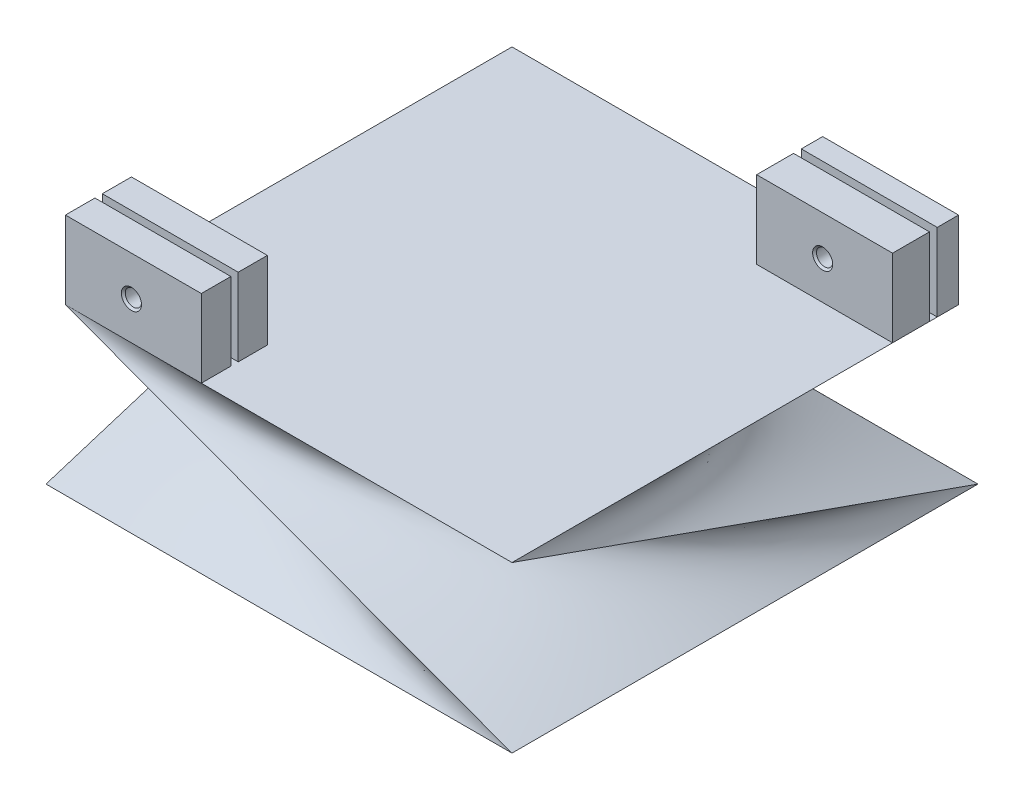
SolidWorks part; units mm, degrees
ref_plane "Front Plane" through (0, 0, 0) normal (0, 0, 1) x (1, 0, 0)
ref_plane "Top Plane" through (0, 0, 0) normal (0, 1, 0) x (1, 0, 0)
ref_plane "Right Plane" through (0, 0, 0) normal (1, 0, 0) x (0, 0, -1)
sketch "Sketch1" plane through (0, 0, 0) normal (0, 1, 0) x (1, 0, 0)
  line L1 (-76.2, -76.2) -> (76.2, -76.2)
  line L2 (-76.2, -76.2) -> (-76.2, 76.2)
  line L3 (-76.2, 76.2) -> (76.2, 76.2)
  line L4 (76.2, -76.2) -> (76.2, 76.2)
  line L5 (-76.2, -76.2) -> (76.2, 76.2) construction
  line L6 (-76.2, 76.2) -> (76.2, -76.2) construction
  point P0 (0, 0)
  dimension "D1" = 152.4
  dimension "D2" = 152.4
ref_plane "Plane1" through (0, 50.8, 0) normal (0, 1, 0) x (1, 0, 0)
sketch "Sketch2" plane through (0, 50.8, 0) normal (0, 1, 0) x (1, 0, 0)
  line L0 (-76.2, -76.2) -> (76.2, 76.2) construction
  line L1 (-73.025, -73.025) -> (73.025, -73.025)
  line L2 (-73.025, -73.025) -> (-73.025, 73.025)
  line L3 (-73.025, 73.025) -> (73.025, 73.025)
  line L4 (73.025, -73.025) -> (73.025, 73.025)
  line L5 (-73.025, -73.025) -> (73.025, 73.025) construction
  line L6 (-73.025, 73.025) -> (73.025, -73.025) construction
  point P0 (0, 0)
  dimension "D1" = 146.05
loft "Loft1" add profiles "Sketch2", "Sketch1" connector at (-73.025, 50.8, -73.025) connector at (-76.2, 0, 76.2)
sketch "Sketch20" plane through (0, 50.8, 0) normal (0, 1, 0) x (1, 0, 0)
  line L1 (-73.025, -73.025) -> (-28.575, -73.025)
  line L2 (-73.025, -73.025) -> (-73.025, -51.435)
  line L3 (-73.025, -51.435) -> (-28.575, -51.435)
  line L4 (-28.575, -73.025) -> (-28.575, -51.435)
  line L5 (73.025, 73.025) -> (28.575, 73.025)
  line L6 (73.025, 73.025) -> (73.025, 51.435)
  line L7 (73.025, 51.435) -> (28.575, 51.435)
  line L8 (28.575, 73.025) -> (28.575, 51.435)
  dimension "D1" = 44.45
  dimension "D2" = 21.59
  dimension "D3" = 44.45
  dimension "D4" = 21.59
extrude "Boss-Extrude3" add sketch "Sketch20" along normal blind 25.4
sketch "Sketch22" plane through (0, 76.2, 0) normal (0, 1, 0) x (1, 0, 0)
  line L0 (-28.575, -60.96) -> (-73.025, -60.96)
  line L1 (-28.575, -73.025) -> (-28.575, -51.435) construction
  line L2 (-73.025, -51.435) -> (-73.025, -73.025) construction
  line L3 (-73.025, -63.373) -> (-28.575, -63.373)
  line L4 (-73.025, -51.435) -> (-73.025, -73.025) construction
  line L5 (-28.575, -73.025) -> (-28.575, -51.435) construction
  line L6 (-28.575, -51.435) -> (-73.025, -51.435) construction
  line L7 (-73.025, -73.025) -> (-28.575, -73.025) construction
  line L8 (-28.575, -60.96) -> (-28.575, -63.373)
  line L9 (-73.025, -60.96) -> (-73.025, -63.373)
  dimension "D1" = 9.525
  dimension "D2" = 9.652
extrude "Cut-Extrude2" cut sketch "Sketch22" against normal blind 25.4
sketch "Sketch23" plane through (0, 76.2, 0) normal (0, 1, 0) x (1, 0, 0)
  line L0 (28.575, 66.04) -> (73.025, 66.04)
  line L1 (28.575, 73.025) -> (28.575, 51.435) construction
  line L2 (73.025, 51.435) -> (73.025, 73.025) construction
  line L3 (73.025, 66.04) -> (73.025, 63.5)
  line L4 (73.025, 51.435) -> (73.025, 73.025) construction
  line L5 (73.025, 63.5) -> (28.575, 63.5)
  line L6 (28.575, 73.025) -> (28.575, 51.435) construction
  line L7 (28.575, 63.5) -> (28.575, 66.04)
  line L8 (73.025, 73.025) -> (28.575, 73.025) construction
  dimension "D1" = 2.54
  dimension "D2" = 6.985
extrude "Cut-Extrude3" cut sketch "Sketch23" against normal blind 25.4
hole_wizard "#4 (0.209) Diameter Hole6" positions "Sketch35" profile "Sketch36" hole size "#4" standard "ANSI Inch" end condition through all
sketch "Sketch35" plane through (0, 0, 73.025) normal (0, 0, 1) x (1, 0, 0)
  line L0 (-73.025, 50.8) -> (-28.575, 50.8) construction
  line L1 (-28.575, 76.2) -> (-28.575, 50.8) construction
  point P0 (-51.435, 63.246)
  dimension "D1" = 12.446
  dimension "D2" = 22.86
sketch "Sketch36" plane through (-51.435, 63.246, 73.025) normal (1, 0, 0) x (0, -1, 0)
  line L0 (0, 0) -> (0, 149.2251)
  line L1 (0, 149.2251) -> (2.6543, 149.2251)
  line L2 (2.6543, 149.2251) -> (2.6543, 0.635)
  line L3 (2.6543, 0.635) -> (3.2893, 0)
  line L5 (3.2893, 0) -> (0, 0)
  line L6 (-2.6543, 0.635) -> (-3.2893, 0) construction
  line L11 (0, -6.35) -> (0, 107.95) construction
  dimension "Thru Hole Dia." = 5.3086
  dimension "Thru Hole Depth" = 149.2251
  dimension "Near C'Sink Dia." = 6.5786
  dimension "Near C'Sink Angle" = 90
hole_wizard "#4 (0.209) Diameter Hole7" positions "Sketch37" profile "Sketch38" hole size "#4" standard "ANSI Inch" end condition through all
sketch "Sketch37" plane through (0, 0, -51.435) normal (0, 0, 1) x (1, 0, 0)
  line L0 (-28.575, 50.8) -> (73.025, 50.8) construction
  line L1 (73.025, 76.2) -> (73.025, 50.8) construction
  point P0 (50.165, 63.246)
  dimension "D1" = 12.446
  dimension "D2" = 22.86
sketch "Sketch38" plane through (50.165, 63.246, -51.435) normal (1, 0, 0) x (0, -1, 0)
  line L0 (0, 0) -> (0, 24.7651)
  line L1 (0, 24.7651) -> (2.6543, 24.7651)
  line L2 (2.6543, 24.7651) -> (2.6543, 0.635)
  line L3 (2.6543, 0.635) -> (3.2893, 0)
  line L5 (3.2893, 0) -> (0, 0)
  line L6 (-2.6543, 0.635) -> (-3.2893, 0) construction
  line L11 (0, -6.35) -> (0, 107.95) construction
  dimension "Thru Hole Dia." = 5.3086
  dimension "Thru Hole Depth" = 24.7651
  dimension "Near C'Sink Dia." = 6.5786
  dimension "Near C'Sink Angle" = 90
